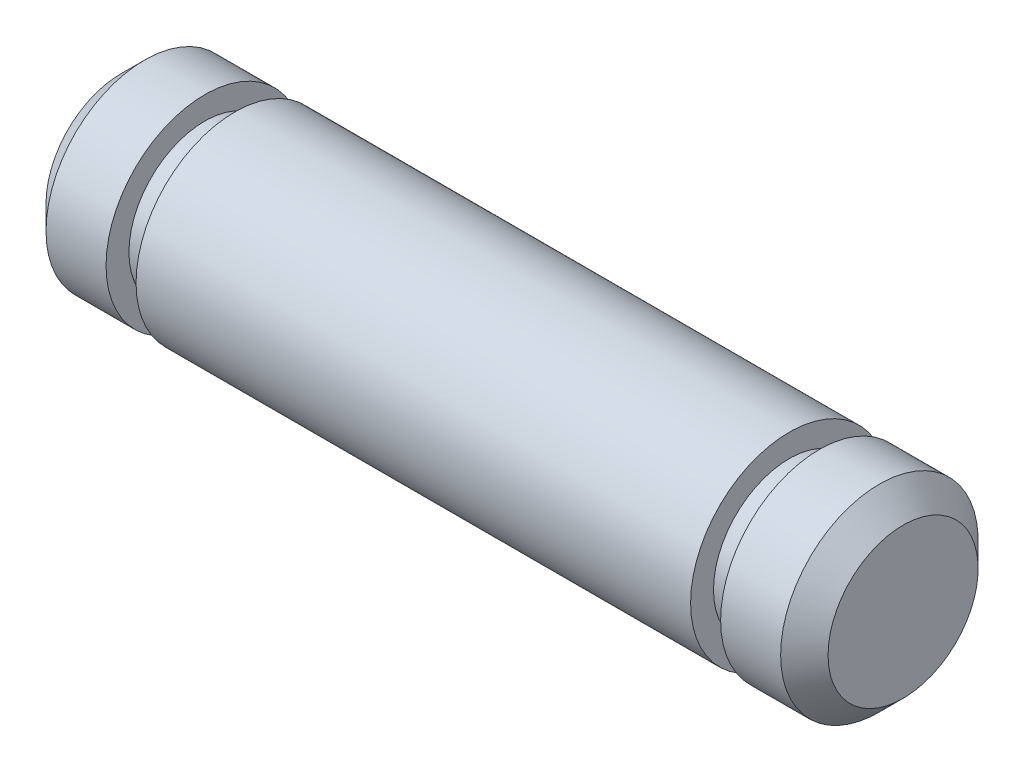
SolidWorks part; units mm, degrees
ref_plane "Front Plane" through (0, 0, 0) normal (0, 0, 1) x (1, 0, 0)
ref_plane "Top Plane" through (0, 0, 0) normal (0, 1, 0) x (1, 0, 0)
ref_plane "Right Plane" through (0, 0, 0) normal (1, 0, 0) x (0, 0, -1)
sketch "Sketch1" plane through (0, 0, 0) normal (0, 0, 1) x (1, 0, 0)
  line L0 (-6.2865, 0) -> (-6.2865, 1.2065)
  line L1 (-6.2865, 1.2065) -> (-5.9055, 1.5875)
  line L2 (-5.9055, 1.5875) -> (-4.9403, 1.5875)
  line L3 (-4.9403, 1.5875) -> (-4.9403, 1.2192)
  line L4 (-4.9403, 1.2192) -> (-4.4577, 1.2192)
  line L5 (-4.4577, 1.2192) -> (-4.4577, 1.5875)
  line L6 (-4.4577, 1.5875) -> (4.4577, 1.5875)
  line L7 (4.4577, 1.5875) -> (4.4577, 1.2192)
  line L8 (4.4577, 1.2192) -> (4.9403, 1.2192)
  line L9 (4.9403, 1.2192) -> (4.9403, 1.5875)
  line L10 (4.9403, 1.5875) -> (5.9055, 1.5875)
  line L11 (5.9055, 1.5875) -> (6.2865, 1.2065)
  line L12 (6.2865, 1.2065) -> (6.2865, 0)
  line L13 (6.2865, 0) -> (-6.2865, 0)
  line L14 (6.2865, 0) -> (-6.2865, 0) construction
revolve "Revolve1" add sketch "Sketch1" angle 360 about L14 reverse direction yes
ref_plane "Plane1" through (4.699, 0, 0) normal (1, 0, 0) x (0, 0, -1)
ref_plane "Plane2" through (-4.699, 0, 0) normal (1, 0, 0) x (0, 0, -1)
ref_plane "p1 XY" through (0, 0, 0) normal (1, 0, 0) x (0, 0, -1)
ref_plane "p1 XZ" through (0, 0, 0) normal (0, -1, 0) x (-1, 0, 0)
ref_plane "p1 YZ" through (0, 0, 1.5875) normal (0, 0, -1) x (-1, 0, 0)
ref_axis "p1 X" through (0, 0, 80.9) along (0, 0, -1)
ref_axis "p1 Y" through (0, -50, 1.5875) along (0, 1, 0)
ref_axis "p1 Z" through (80.9, 0, 1.5875) along (-1, 0, 0)
sketch3d "p1"
  point P0 (0, 0, 1.5875)
ref_plane "p2 XY" through (0, 0, 0) normal (1, 0, 0) x (0, 0, -1)
ref_plane "p2 XZ" through (0, 0, 0) normal (0, -1, 0) x (-1, 0, 0)
ref_plane "p2 YZ" through (0, 0, -1.5875) normal (0, 0, -1) x (-1, 0, 0)
ref_axis "p2 X" through (0, 0, 80.9) along (0, 0, -1)
ref_axis "p2 Y" through (0, -50, -1.5875) along (0, 1, 0)
ref_axis "p2 Z" through (80.9, 0, -1.5875) along (-1, 0, 0)
sketch3d "p2"
  point P0 (0, 0, -1.5875)
ref_plane "pin XY" through (0, 0, 0) normal (1, 0, 0) x (0, 0, -1)
ref_plane "pin XZ" through (0, 0, 0) normal (0, -1, 0) x (-1, 0, 0)
ref_plane "pin YZ" through (0, 0, 0) normal (0, 0, -1) x (-1, 0, 0)
ref_axis "pin X" through (0, 0, 80.9) along (0, 0, -1)
ref_axis "pin Y" through (0, -50, 0) along (0, 1, 0)
ref_axis "pin Z" through (80.9, 0, 0) along (-1, 0, 0)
sketch3d "pin"
  point P0 (0, 0, 0)
ref_plane "rr1 XY" through (4.699, 0, 0) normal (1, 0, 0) x (0, 0, -1)
ref_plane "rr1 XZ" through (0, 0, 0) normal (0, -1, 0) x (-1, 0, 0)
ref_plane "rr1 YZ" through (0, 0, 0) normal (0, 0, -1) x (-1, 0, 0)
ref_axis "rr1 X" through (4.699, 0, 80.9) along (0, 0, -1)
ref_axis "rr1 Y" through (4.699, -50, 0) along (0, 1, 0)
ref_axis "rr1 Z" through (80.9, 0, 0) along (-1, 0, 0)
sketch3d "rr1"
  point P0 (4.699, 0, 0)
ref_plane "rr2 XY" through (-4.699, 0, 0) normal (1, 0, 0) x (0, 0, -1)
ref_plane "rr2 XZ" through (0, 0, 0) normal (0, -1, 0) x (-1, 0, 0)
ref_plane "rr2 YZ" through (0, 0, 0) normal (0, 0, -1) x (-1, 0, 0)
ref_axis "rr2 X" through (-4.699, 0, 80.9) along (0, 0, -1)
ref_axis "rr2 Y" through (-4.699, -50, 0) along (0, 1, 0)
ref_axis "rr2 Z" through (80.9, 0, 0) along (-1, 0, 0)
sketch3d "rr2"
  point P0 (-4.699, 0, 0)
ref_plane "w21 XY" through (0, 0, 0) normal (0, 1, 0) x (1, 0, 0)
ref_plane "w21 XZ" through (0, 0, 0) normal (0, 0, 1) x (1, 0, 0)
ref_plane "w21 YZ" through (6.2865, 0, 0) normal (1, 0, 0) x (0, 0, -1)
ref_axis "w21 X" through (-80.9, 0, 0) along (1, 0, 0)
ref_axis "w21 Y" through (6.2865, 0, 50) along (0, 0, -1)
ref_axis "w21 Z" through (6.2865, 50, 0) along (0, -1, 0)
sketch3d "w21"
  point P0 (6.2865, 0, 0)
ref_plane "w22 XY" through (0, 0, 0) normal (0, 1, 0) x (1, 0, 0)
ref_plane "w22 XZ" through (0, 0, 0) normal (0, 0, 1) x (1, 0, 0)
ref_plane "w22 YZ" through (-6.2865, 0, 0) normal (1, 0, 0) x (0, 0, -1)
ref_axis "w22 X" through (-80.9, 0, 0) along (1, 0, 0)
ref_axis "w22 Y" through (-6.2865, 0, 50) along (0, 0, -1)
ref_axis "w22 Z" through (-6.2865, 50, 0) along (0, -1, 0)
sketch3d "w22"
  point P0 (-6.2865, 0, 0)
